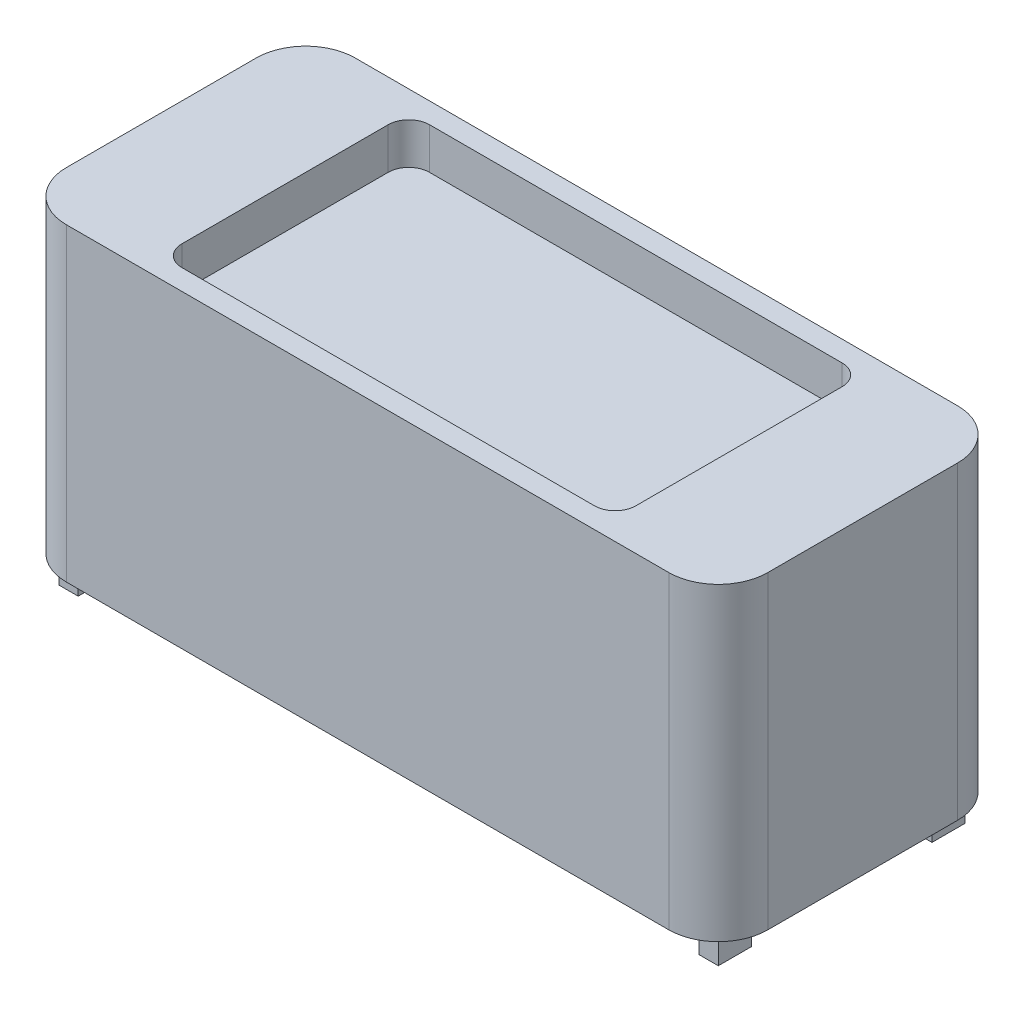
SolidWorks part; units mm, degrees
ref_plane "Front Plane" through (0, 0, 0) normal (0, 0, 1) x (1, 0, 0)
ref_plane "Top Plane" through (0, 0, 0) normal (0, 1, 0) x (1, 0, 0)
ref_plane "Right Plane" through (0, 0, 0) normal (1, 0, 0) x (0, 0, -1)
sketch "Sketch1" plane through (0, 0, 0) normal (0, 1, 0) x (1, 0, 0)
  line L6 (-730, 350) -> (730, 350)
  line L10 (-850, 230) -> (-850, -230)
  line L11 (-730, -350) -> (730, -350)
  line L12 (850, 230) -> (850, -230)
  line L13 (-850, 350) -> (850, -350) construction
  line L14 (-850, -350) -> (850, 350) construction
  line L15 (-550, 300) -> (550, 300)
  line L16 (-550, 300) -> (-550, -300)
  line L17 (-550, -300) -> (550, -300)
  line L18 (550, 300) -> (550, -300)
  line L19 (-550, 300) -> (550, -300) construction
  line L20 (-550, -300) -> (550, 300) construction
  line L21 (813, -141.1234) -> (587, -141.1234) construction
  line L22 (813, -141.1234) -> (813, 0) construction
  line L23 (813, 0) -> (587, 0) construction
  line L24 (587, -141.1234) -> (587, 0) construction
  line L25 (813, -141.1234) -> (587, 0) construction
  line L26 (813, 0) -> (587, -141.1234) construction
  arc A0 (730, -350) -> (850, -230) centre (730, -230) ccw
  arc A1 (-850, -230) -> (-730, -350) centre (-730, -230) ccw
  arc A2 (730, 350) -> (850, 230) centre (730, 230) cw
  arc A3 (-730, 350) -> (-850, 230) centre (-730, 230) ccw
  point P0 (0, 0)
  point P5 (700, -70.5617)
  point P6 (0, 0)
  dimension "D5" = 120
  dimension "D2" = 1700
  dimension "D3" = 1100
  dimension "D1" = 700
  dimension "D4" = 600
  dimension "D6" = 226
  dimension "D7" = 700
extrude "Boss-Extrude1" add sketch "Sketch1" against normal blind 750 contours L6 A3 L10 A1 L11 A0 L12 A2 L15 L18 L17 L16 | A3 L6 A2 L12 A0 L11 A1 L10 region at (0, 0, -331.6152)
extrude "Cut-Extrude1" cut sketch "Sketch1<3>" against normal blind 100 contours L18 L15 L16 L17 region at (0, 0, 0)
sketch "Sketch1<3>" plane through (0, 0, 0) normal (0, 1, 0) x (1, 0, 0) same geometry as "Sketch1"
fillet "Fillet1" radius 50 4 edges at (550, -50, 300) (-550, -50, 300) (550, -50, -300) (-550, -50, -300)
sketch "Sketch2" plane through (0, -750, 0) normal (0, -1, 0) x (1, 0, 0)
  line L0 (-850, -230) -> (-850, 230) construction
  line L1 (-799.2, 299.2) -> (-752.2, 299.2)
  line L2 (-799.2, 299.2) -> (-799.2, 218.7)
  line L3 (-799.2, 218.7) -> (-752.2, 218.7)
  line L4 (-752.2, 299.2) -> (-752.2, 218.7)
  line L5 (-730, 350) -> (730, 350) construction
  line L6 (0, 350) -> (0, -350) construction
  line L7 (-730, -350) -> (730, -350) construction
  line L8 (-850, 0) -> (850, 0) construction
  line L9 (850, -230) -> (850, 230) construction
  line L10 (799.2, 218.7) -> (752.2, 218.7)
  line L11 (752.2, 299.2) -> (752.2, 218.7)
  line L12 (799.2, 299.2) -> (752.2, 299.2)
  line L13 (799.2, 299.2) -> (799.2, 218.7)
  line L14 (799.2, -299.2) -> (799.2, -218.7)
  line L15 (799.2, -299.2) -> (752.2, -299.2)
  line L16 (752.2, -299.2) -> (752.2, -218.7)
  line L17 (799.2, -218.7) -> (752.2, -218.7)
  line L18 (-799.2, -218.7) -> (-752.2, -218.7)
  line L19 (-752.2, -299.2) -> (-752.2, -218.7)
  line L20 (-799.2, -299.2) -> (-752.2, -299.2)
  line L21 (-799.2, -299.2) -> (-799.2, -218.7)
  dimension "D1" = 50.8
  dimension "D2" = 50.8
  dimension "D3" = 80.5
  dimension "D4" = 47
extrude "Boss-Extrude2" add sketch "Sketch2" along normal blind 66.215
